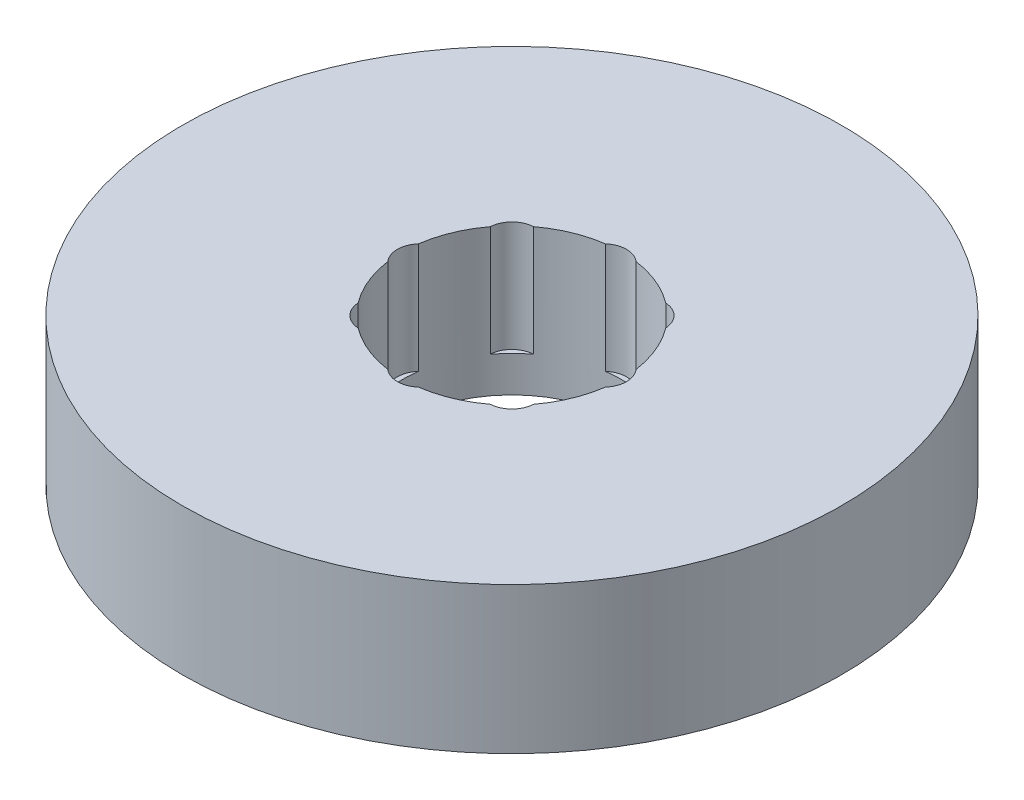
SolidWorks part; units mm, degrees
ref_plane "Front Plane" through (0, 0, 0) normal (0, 0, 1) x (1, 0, 0)
ref_plane "Top Plane" through (0, 0, 0) normal (0, 1, 0) x (1, 0, 0)
ref_plane "Right Plane" through (0, 0, 0) normal (1, 0, 0) x (0, 0, -1)
sketch "Sketch1" plane through (0, 0, 0) normal (0, 1, 0) x (1, 0, 0)
  circle A0 centre (0, 0) radius 22.5
  dimension "FLANGE_OD" = 45
extrude "Boss-Extrude1" add sketch "Sketch1" along normal blind 10
sketch "Sketch2" plane through (0, 0, 0) normal (0, 1, 0) x (1, 0, 0)
  circle A0 centre (0, 0) radius 7.5
  dimension "BORE_D" = 15
extrude "Cut-Extrude1" cut sketch "Sketch2" along normal through all
sketch "Sketch3" plane through (0, 10, 0) normal (0, 1, 0) x (1, 0, 0)
  circle A0 centre (0, 0) radius 6.2453 construction
  circle A1 centre (-6.2453, 0) radius 1.578
  dimension "BOLT_D" = 3.1561
  dimension "BOLT_PCD" = 12.4906
extrude "Cut-Extrude2" cut sketch "Sketch3" against normal blind 7.5407
pattern_circular "CirPattern1" count 8 over 360 about axis through (0, 0, 0) along (0, 1, 0) of "Cut-Extrude2"
